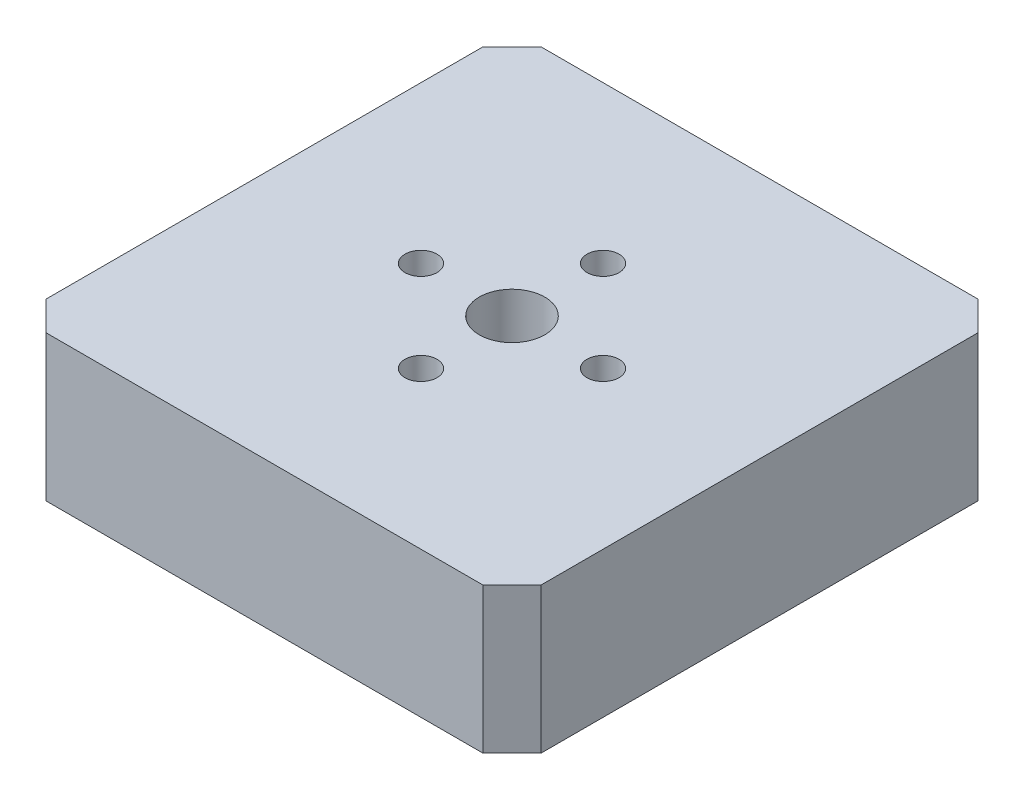
SolidWorks part; units mm, degrees
material "ABS"
ref_plane "前视基准面" through (0, 0, 0) normal (0, 0, 1) x (1, 0, 0)
ref_plane "上视基准面" through (0, 0, 0) normal (0, 1, 0) x (1, 0, 0)
ref_plane "右视基准面" through (0, 0, 0) normal (1, 0, 0) x (0, 0, -1)
sketch "草图1" plane through (0, 0, 0) normal (0, 1, 0) x (1, 0, 0)
  line L1 (-15, -15) -> (15, -15)
  line L2 (-15, -15) -> (-15, 15)
  line L3 (-15, 15) -> (15, 15)
  line L4 (15, -15) -> (15, 15)
  line L5 (-15, -15) -> (15, 15) construction
  line L6 (-15, 15) -> (15, -15) construction
  line L7 (-17, -17) -> (17, -17)
  line L8 (-17, -17) -> (-17, 17)
  line L9 (-17, 17) -> (17, 17)
  line L10 (17, -17) -> (17, 17)
  line L11 (-17, -17) -> (17, 17) construction
  line L12 (-17, 17) -> (17, -17) construction
  circle A0 centre (0, 0) radius 2.25
  point P0 (0, 0)
  point P6 (0, 0)
  dimension "D4" = 4.5
  dimension "D1" = 30
  dimension "D2" = 90
  dimension "D3" = 2
extrude "凸台-拉伸1" add sketch "草图1" along normal blind 10 contours A0 | L9 L10 L7 L8 region at (0, 0, 0)
extrude "切除-拉伸1" cut sketch "草图1<3>" along normal blind 6 contours L1 L4 L3 L2 region at (-14.5757, 0, 0)
sketch "草图1<3>" plane through (0, 0, 0) normal (0, 1, 0) x (1, 0, 0) same geometry as "草图1"
chamfer "倒角1" distance 2 angle 45 8 edges at (-15, 3, -15) (15, 3, -15) (15, 3, 15) (-15, 3, 15) (-17, 5, 17) (17, 5, 17) (17, 5, -17) (-17, 5, -17)
sketch "草图4" plane through (0, 6, 0) normal (0, -1, 0) x (-1, 0, 0)
  point P0 (0, 6.25)
  point P6 (6.25, 0)
  point P7 (0, -6.25)
  point P8 (-6.25, 0)
  dimension "D2" = 12.5
  dimension "D1" = 4
hole_wizard "M2 六角圆柱头螺钉的柱形沉头孔1" positions "草图4" profile "草图3" counterbore size "M2" standard "GB" end condition through all
sketch "草图3" plane through (0, 6, -6.25) normal (1, 0, 0) x (0, 0, -1)
  line L0 (0, 0) -> (0, 4)
  line L1 (0, 4) -> (1.1, 4)
  line L3 (1.1, 4) -> (1.1, 2.3)
  line L4 (1.1, 2.3) -> (2.15, 2.3)
  line L5 (2.15, 2.3) -> (2.15, 0)
  line L7 (2.15, 0) -> (0, 0)
  line L11 (0, -6.35) -> (0, 107.95) construction
  dimension "通孔孔直径" = 2.2
  dimension "通孔孔深度" = 4
  dimension "柱形沉头孔直径" = 4.3
  dimension "柱形沉头孔深度" = 2.3
